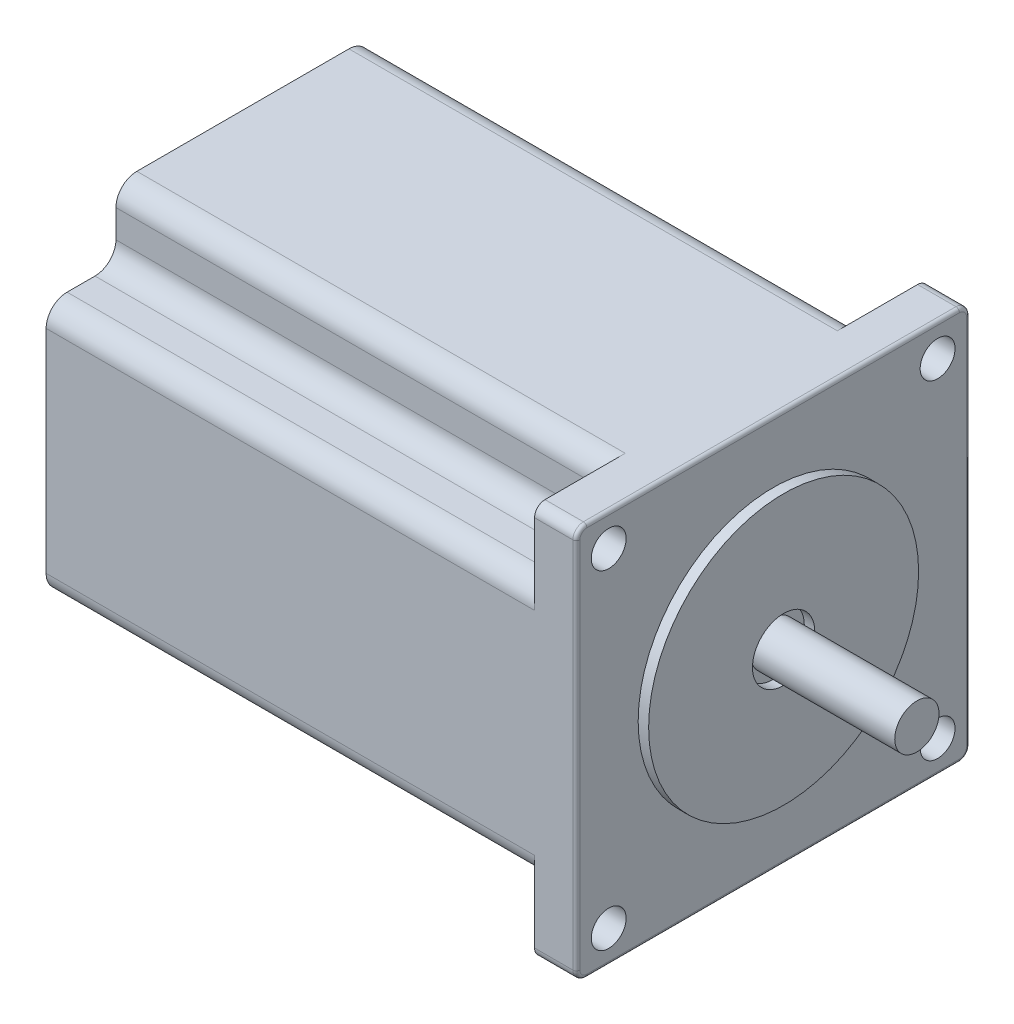
SolidWorks part; units mm, degrees
ref_plane "Front Plane" through (0, 0, 0) normal (0, 0, 1) x (1, 0, 0)
ref_plane "Top Plane" through (0, 0, 0) normal (0, 1, 0) x (1, 0, 0)
ref_plane "Right Plane" through (0, 0, 0) normal (1, 0, 0) x (0, 0, -1)
sketch "Sketch1" plane through (0, 0, 0) normal (0, 1, 0) x (1, 0, 0)
  line L1 (-50.2578, 17.3245) -> (25.7422, 17.3245)
  line L2 (-50.2578, 17.3245) -> (-50.2578, -39.0755)
  line L3 (-50.2578, -39.0755) -> (25.7422, -39.0755)
  line L4 (25.7422, 17.3245) -> (25.7422, -39.0755)
  dimension "D1" = 76
  dimension "D2" = 56.4
extrude "Boss-Extrude1" add sketch "Sketch1" along normal blind 56.4
sketch "Sketch2" plane through (0, 0, 39.0755) normal (0, 0, 1) x (1, 0, 0)
  line L1 (-50.2578, 56.4) -> (19.7422, 56.4)
  line L2 (-50.2578, 56.4) -> (-50.2578, 46.4)
  line L3 (-50.2578, 46.4) -> (19.7422, 46.4)
  line L4 (19.7422, 56.4) -> (19.7422, 46.4)
  dimension "D1" = 70
  dimension "D2" = 10
extrude "Cut-Extrude1" cut sketch "Sketch2" against normal blind 10 contours L4 L3 L2 L1
sketch "Sketch3" plane through (0, 0, -17.3245) normal (0, 0, -1) x (-1, 0, 0)
  line L1 (-25.7422, 56.4) -> (50.2578, 56.4) construction
  line L2 (-19.7422, 56.4) -> (50.2578, 56.4)
  line L3 (-19.7422, 56.4) -> (-19.7422, 46.4)
  line L4 (-19.7422, 46.4) -> (50.2578, 46.4)
  line L5 (50.2578, 56.4) -> (50.2578, 46.4)
  line L6 (50.2578, 0) -> (-19.7422, 0)
  line L7 (50.2578, 0) -> (50.2578, 10)
  line L8 (50.2578, 10) -> (-19.7422, 10)
  line L9 (-19.7422, 0) -> (-19.7422, 10)
  line L10 (50.2578, 56.4) -> (50.2578, 0) construction
  dimension "D1" = 70
  dimension "D2" = 10
  dimension "D3" = 10
extrude "Cut-Extrude4" cut sketch "Sketch3" against normal blind 10 contours L8 L9 L6 L7 | L4 L5 L2 L3
sketch "Sketch5" plane through (0, 0, 0) normal (0, -1, 0) x (1, 0, 0)
  line L1 (-50.2578, 39.0755) -> (19.7422, 39.0755)
  line L2 (-50.2578, 39.0755) -> (-50.2578, 29.0755)
  line L3 (-50.2578, 29.0755) -> (19.7422, 29.0755)
  line L4 (19.7422, 39.0755) -> (19.7422, 29.0755)
  dimension "D1" = 10
extrude "Cut-Extrude5" cut sketch "Sketch5" against normal blind 10 contours L3 L4 L1 L2
fillet "Fillet2" radius 3 8 edges at (-15.2578, 10, 39.0755) (-15.2578, 0, 29.0755) (-15.2578, 0, -7.3245) (-15.2578, 10, -17.3245) (-15.2578, 46.4, -17.3245) (-15.2578, 56.4, -7.3245) (-15.2578, 56.4, 29.0755) (-15.2578, 46.4, 39.0755)
fillet "Fillet3" radius 3 4 edges at (-15.2578, 46.4, -7.3245) (-15.2578, 10, -7.3245) (-15.2578, 10, 29.0755) (-15.2578, 46.4, 29.0755)
sketch "Sketch7" plane through (-50.2578, 0, 0) normal (-1, 0, 0) x (0, 0, 1)
  circle A0 centre (11.5755, 27.5) radius 5
  dimension "D1" = 10
extrude "Cut-Extrude6" cut sketch "Sketch7" against normal blind 5
fillet "Fillet4" radius 1 1 edges at (-50.2578, 27.5, 16.5755)
fillet "Fillet5" radius 0.5 4 edges at (25.7422, 28.2, -17.3245) (25.7422, 0, 10.8755) (25.7422, 28.2, 39.0755) (25.7422, 56.4, 10.8755)
fillet "Fillet6" radius 1.5 2 edges at (25.5957, 56.2536, 38.929) (22.4922, 56.4, 39.0755)
fillet "Fillet7" radius 1.5 6 edges at (25.5957, 56.2536, -17.1781) (25.5957, 0.1464, 38.929) (25.5957, 0.1464, -17.1781) (22.4922, 0, -17.3245) (22.4922, 0, 39.0755) (22.4922, 56.4, -17.3245)
sketch "Sketch18" plane through (25.7422, 0, 0) normal (1, 0, 0) x (0, 0, -1)
  line L0 (-10.8755, 56.4) -> (-10.8755, 0)
  line L1 (-10.8755, 28.2) -> (-10.8755, 4.63)
  line L3 (-37.5755, 56.4) -> (15.8245, 56.4) construction
  line L4 (15.8245, 0) -> (-37.5755, 0) construction
  line L5 (-10.8755, 28.2) -> (17.3245, 28.2)
  line L6 (17.3245, 54.9) -> (17.3245, 1.5) construction
  line L7 (-10.8755, 28.2) -> (-39.0755, 28.2)
  line L8 (-39.0755, 1.5) -> (-39.0755, 54.9) construction
  line L9 (-10.8755, 28.2) -> (-10.8755, 3.4287)
  line L13 (-34.4455, 4.63) -> (-10.8755, 4.63)
  circle A0 centre (-34.4455, 51.77) radius 2.5
  circle A1 centre (12.6945, 51.77) radius 2.5
  circle A2 centre (12.6945, 4.63) radius 2.5
  circle A3 centre (-34.4455, 4.63) radius 2.5
  circle A4 centre (-10.8755, 28.2) radius 3.175
  dimension "D1" = 5
  dimension "D2" = 5
  dimension "D3" = 5
  dimension "D4" = 5
  dimension "D5" = 6.35
extrude "Cut-Extrude7" cut sketch "Sketch18" against normal blind 10 contours A1 | A2 | A3 | A0 region at (25.7422, 4.63, 36.8748) region at (25.7422, 51.77, 34.4455) region at (25.7422, 51.77, -12.6945) region at (25.7422, 4.63, -12.6945)
sketch "Sketch20" plane through (25.7422, 0, 0) normal (1, 0, 0) x (0, 0, -1)
  circle A0 centre (-10.8755, 28.2) radius 3.175
  dimension "D1" = 6.35
extrude "Boss-Extrude2" add sketch "Sketch20" along normal blind 20.6
sketch "Sketch21" plane through (25.7422, 0, 0) normal (1, 0, 0) x (0, 0, -1)
  circle A0 centre (-10.8755, 28.2) radius 4.4683
  circle A1 centre (-10.8755, 28.2) radius 19.3485
extrude "Boss-Extrude3" add sketch "Sketch21" along normal blind 1.5
